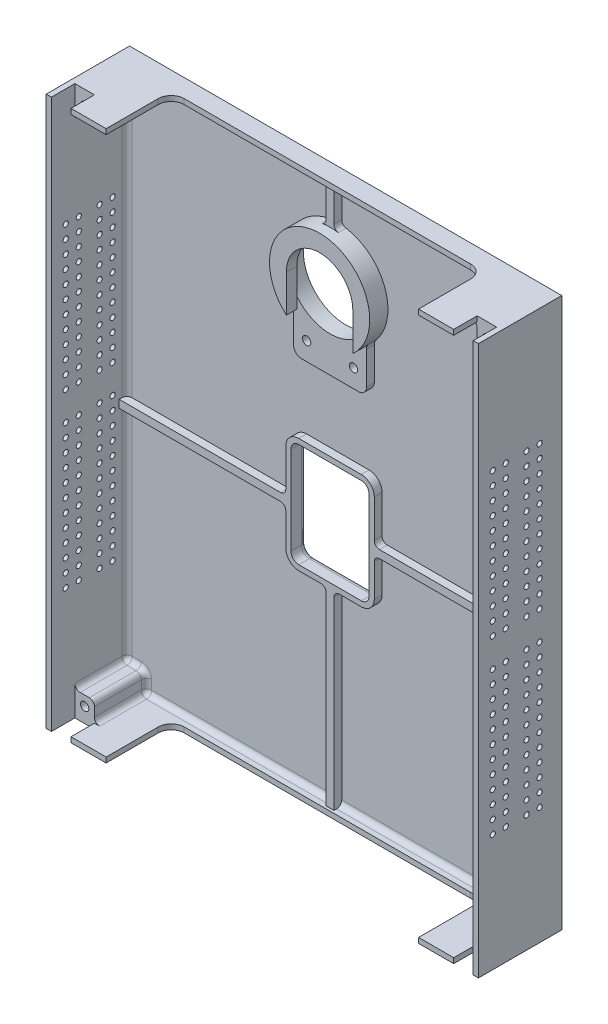
SolidWorks part; units mm, degrees
ref_plane "Front Plane" through (0, 0, 0) normal (0, 0, 1) x (1, 0, 0)
ref_plane "Top Plane" through (0, 0, 0) normal (0, 1, 0) x (1, 0, 0)
ref_plane "Right Plane" through (0, 0, 0) normal (1, 0, 0) x (0, 0, -1)
ref_plane "Plane1" through (0, 0, -1) normal (0, 0, 1) x (1, 0, 0)
sketch "Sketch5" plane through (0, 0, -1) normal (0, 0, 1) x (1, 0, 0)
  line L0 (100, 83.2573) -> (100, -169.2647) construction
  line L2 (17, 83.2573) -> (17, -127.7573)
  line L3 (17, -127.7573) -> (183, -127.7573)
  line L4 (183, 83.2573) -> (183, -127.7573)
  line L5 (17, 83.2573) -> (183, 83.2573)
  circle A0 centre (100, 48.2573) radius 16.25
  point P17 (45, 83.2573)
  dimension "D1" = 166
  dimension "D2" = 83
extrude "Boss-Extrude5" add sketch "Sketch5" along normal blind 3
sketch "Sketch6" plane through (0, 0, 2) normal (0, 0, 1) x (1, 0, 0)
  line L0 (116.25, 48.2573) -> (83.75, 48.2573) construction
  line L2 (86, 35.0451) -> (86, 18.2573)
  line L3 (86, 18.2573) -> (114, 18.2573)
  line L4 (114, 35.0451) -> (114, 18.2573)
  line L5 (100, 48.2573) -> (100, 52.872) construction
  circle A1 centre (100, 48.2573) radius 16.25
  arc A2 (114, 35.0451) -> (86, 35.0451) centre (100, 48.2573) ccw
  circle A6 centre (100, 48.2573) radius 16.25 construction
extrude "Boss-Extrude6" add sketch "Sketch6" along normal blind 3
sketch "Sketch7" plane through (0, 0, 5) normal (0, 0, 1) x (1, 0, 0)
  line L0 (112.75, 33.8351) -> (112.75, 48.2573)
  line L2 (87.25, 48.2573) -> (87.25, 33.8351)
  line L3 (100, 64.5073) -> (100, 48.2573) construction
  line L4 (100, 48.2573) -> (116.25, 48.2573) construction
  arc A8 (112.75, 33.8351) -> (87.25, 33.8351) centre (100, 48.2573) ccw
  circle A9 centre (100, 48.2573) radius 19.25 construction
  circle A10 centre (100, 48.2573) radius 16.25 construction
  circle A12 centre (100, 48.2573) radius 12.75
  arc A13 (112.75, 48.2573) -> (87.25, 48.2573) centre (100, 48.2573) ccw
  dimension "D1" = 1
extrude "Boss-Extrude7" add sketch "Sketch7" along normal blind 4
sketch "Sketch8" plane through (0, 0, 2) normal (0, 0, 1) x (1, 0, 0)
  line L4 (17, -127.7573) -> (183, -127.7573)
  line L5 (183, -127.7573) -> (183, 83.2573)
  line L6 (183, 83.2573) -> (17, 83.2573)
  line L7 (17, 83.2573) -> (17, -127.7573)
  line L8 (17, -127.7573) -> (183, -127.7573)
  line L9 (183, -127.7573) -> (183, 83.2573)
  line L10 (183, 83.2573) -> (17, 83.2573)
  line L11 (17, 83.2573) -> (17, -127.7573)
  line L12 (19, -125.7573) -> (181, -125.7573)
  line L13 (181, -125.7573) -> (181, 81.2573)
  line L14 (181, 81.2573) -> (19, 81.2573)
  line L15 (19, 81.2573) -> (19, -125.7573)
  dimension "D1" = 0
  dimension "D2" = 2
extrude "Boss-Extrude8" add sketch "Sketch8" along normal blind 29
fillet "Fillet2" radius 3 4 edges at (114, 18.2573, 3.5) (114, 35.0451, 3.5) (86, 18.2573, 3.5) (86, 35.0451, 3.5)
sketch "Sketch9" plane through (0, 0, 5) normal (0, 0, 1) x (1, 0, 0)
  line L0 (100, 48.2573) -> (100, 25.2573) construction
  line L1 (91, 25.2573) -> (109, 25.2573) construction
  line L2 (100, 25.2573) -> (100, 23.2329) construction
  circle A0 centre (91, 25.2573) radius 1.6
  circle A1 centre (109, 25.2573) radius 1.6
extrude "Cut-Extrude1" cut sketch "Sketch9" against normal up to surface (6 mm away) up to face at (100, -22.25, -1)
sketch "Sketch12" plane through (183, 0, 0) normal (1, 0, 0) x (0, 0, -1)
  circle A0 centre (-12.5, -16.7427) radius 1
  circle A1 centre (-7.5, -16.7427) radius 1
  circle A2 centre (-7.5, -11.7427) radius 1
  circle A3 centre (-7.5, -6.7427) radius 1
  circle A4 centre (-7.5, -1.7427) radius 1
  circle A5 centre (-7.5, 3.2573) radius 1
  circle A6 centre (-7.5, 8.2573) radius 1
  circle A7 centre (-7.5, 13.2573) radius 1
  circle A8 centre (-7.5, 18.2573) radius 1
  circle A9 centre (-7.5, 23.2573) radius 1
  circle A10 centre (-7.5, 28.2573) radius 1
  circle A11 centre (-7.5, 33.2573) radius 1
  circle A12 centre (-7.5, 38.2573) radius 1
  circle A13 centre (-12.5, -11.7427) radius 1
  circle A14 centre (-12.5, -6.7427) radius 1
  circle A15 centre (-12.5, -1.7427) radius 1
  circle A16 centre (-12.5, 3.2573) radius 1
  circle A17 centre (-12.5, 8.2573) radius 1
  circle A18 centre (-12.5, 13.2573) radius 1
  circle A19 centre (-12.5, 18.2573) radius 1
  circle A20 centre (-12.5, 23.2573) radius 1
  circle A21 centre (-12.5, 28.2573) radius 1
  circle A22 centre (-12.5, 33.2573) radius 1
  circle A23 centre (-12.5, 38.2573) radius 1
  circle A24 centre (-12.5, -82.7573) radius 1
  circle A25 centre (-12.5, -77.7573) radius 1
  circle A26 centre (-12.5, -72.7573) radius 1
  circle A27 centre (-12.5, -67.7573) radius 1
  circle A28 centre (-12.5, -62.7573) radius 1
  circle A29 centre (-12.5, -57.7573) radius 1
  circle A30 centre (-12.5, -52.7573) radius 1
  circle A31 centre (-12.5, -47.7573) radius 1
  circle A32 centre (-12.5, -42.7573) radius 1
  circle A33 centre (-12.5, -37.7573) radius 1
  circle A34 centre (-12.5, -32.7573) radius 1
  circle A35 centre (-7.5, -82.7573) radius 1
  circle A36 centre (-7.5, -77.7573) radius 1
  circle A37 centre (-7.5, -72.7573) radius 1
  circle A38 centre (-7.5, -67.7573) radius 1
  circle A39 centre (-7.5, -62.7573) radius 1
  circle A40 centre (-7.5, -57.7573) radius 1
  circle A41 centre (-7.5, -52.7573) radius 1
  circle A42 centre (-7.5, -47.7573) radius 1
  circle A43 centre (-7.5, -42.7573) radius 1
  circle A44 centre (-7.5, -37.7573) radius 1
  circle A45 centre (-7.5, -32.7573) radius 1
  circle A46 centre (-7.5, -27.7573) radius 1
  circle A47 centre (-12.5, -27.7573) radius 1
  circle A48 centre (-20.5, -27.7573) radius 1
  circle A49 centre (-25.5, -27.7573) radius 1
  circle A50 centre (-25.5, -32.7573) radius 1
  circle A51 centre (-25.5, -37.7573) radius 1
  circle A52 centre (-25.5, -42.7573) radius 1
  circle A53 centre (-25.5, -47.7573) radius 1
  circle A54 centre (-25.5, -52.7573) radius 1
  circle A55 centre (-25.5, -57.7573) radius 1
  circle A56 centre (-25.5, -62.7573) radius 1
  circle A57 centre (-25.5, -67.7573) radius 1
  circle A58 centre (-25.5, -72.7573) radius 1
  circle A59 centre (-25.5, -77.7573) radius 1
  circle A60 centre (-25.5, -82.7573) radius 1
  circle A61 centre (-20.5, -32.7573) radius 1
  circle A62 centre (-20.5, -37.7573) radius 1
  circle A63 centre (-20.5, -42.7573) radius 1
  circle A64 centre (-20.5, -47.7573) radius 1
  circle A65 centre (-20.5, -52.7573) radius 1
  circle A66 centre (-20.5, -57.7573) radius 1
  circle A67 centre (-20.5, -62.7573) radius 1
  circle A68 centre (-20.5, -67.7573) radius 1
  circle A69 centre (-20.5, -72.7573) radius 1
  circle A70 centre (-20.5, -77.7573) radius 1
  circle A71 centre (-20.5, -82.7573) radius 1
  circle A72 centre (-20.5, 38.2573) radius 1
  circle A73 centre (-20.5, 33.2573) radius 1
  circle A74 centre (-20.5, 28.2573) radius 1
  circle A75 centre (-20.5, 23.2573) radius 1
  circle A76 centre (-20.5, 18.2573) radius 1
  circle A77 centre (-20.5, 13.2573) radius 1
  circle A78 centre (-20.5, 8.2573) radius 1
  circle A79 centre (-20.5, 3.2573) radius 1
  circle A80 centre (-20.5, -1.7427) radius 1
  circle A81 centre (-20.5, -6.7427) radius 1
  circle A82 centre (-20.5, -11.7427) radius 1
  circle A83 centre (-25.5, 38.2573) radius 1
  circle A84 centre (-25.5, 33.2573) radius 1
  circle A85 centre (-25.5, 28.2573) radius 1
  circle A86 centre (-25.5, 23.2573) radius 1
  circle A87 centre (-25.5, 18.2573) radius 1
  circle A88 centre (-25.5, 13.2573) radius 1
  circle A89 centre (-25.5, 8.2573) radius 1
  circle A90 centre (-25.5, 3.2573) radius 1
  circle A91 centre (-25.5, -1.7427) radius 1
  circle A92 centre (-25.5, -6.7427) radius 1
  circle A93 centre (-25.5, -11.7427) radius 1
  circle A94 centre (-25.5, -16.7427) radius 1
  circle A95 centre (-20.5, -16.7427) radius 1
  dimension "D1" = 2
  dimension "D2" = 12
extrude "Cut-Extrude4" cut sketch "Sketch12" against normal up to surface (2 mm away) up to face at (181, -22.25, 16.5)
sketch "Sketch13" plane through (0, 0, -1) normal (0, 0, -1) x (-1, 0, 0)
  line L0 (-183, -30.7808) -> (-100, -30.7808) construction
  line L1 (-183, -127.7573) -> (-183, 83.2573) construction
  line L6 (-100, 83.2573) -> (-100, -30.7808) construction
  line L7 (-183, 83.2573) -> (-17, 83.2573) construction
  line L14 (-85, -47.7808) -> (-85, -13.7808)
  line L15 (-88, -10.7808) -> (-112, -10.7808)
  line L16 (-115, -13.7808) -> (-115, -47.7808)
  line L17 (-112, -50.7808) -> (-88, -50.7808)
  circle A1 centre (-100, -30.7808) radius 9 construction
  arc A15 (-88, -50.7808) -> (-85, -47.7808) centre (-88, -47.7808) ccw
  arc A16 (-85, -13.7808) -> (-88, -10.7808) centre (-88, -13.7808) ccw
  arc A17 (-112, -10.7808) -> (-115, -13.7808) centre (-112, -13.7808) ccw
  arc A18 (-115, -47.7808) -> (-112, -50.7808) centre (-112, -47.7808) ccw
extrude "Cut-Extrude5" cut sketch "Sketch13" against normal blind 3
sketch "Sketch14" plane through (17, 0, 0) normal (-1, 0, 0) x (0, 0, 1)
  circle A1 centre (12.5, -82.7573) radius 1
  circle A2 centre (12.5, -82.7573) radius 1
  circle A3 centre (12.5, -16.7427) radius 1
  circle A4 centre (12.5, -16.7427) radius 1
  circle A5 centre (7.5, 18.2573) radius 1
  circle A6 centre (7.5, 18.2573) radius 1
  circle A7 centre (7.5, 13.2573) radius 1
  circle A8 centre (7.5, 13.2573) radius 1
  circle A9 centre (7.5, 8.2573) radius 1
  circle A10 centre (7.5, 8.2573) radius 1
  circle A11 centre (7.5, 3.2573) radius 1
  circle A12 centre (7.5, 3.2573) radius 1
  circle A13 centre (7.5, -1.7427) radius 1
  circle A14 centre (7.5, -1.7427) radius 1
  circle A15 centre (7.5, -6.7427) radius 1
  circle A16 centre (7.5, -6.7427) radius 1
  circle A17 centre (7.5, -11.7427) radius 1
  circle A18 centre (7.5, -11.7427) radius 1
  circle A19 centre (7.5, -16.7427) radius 1
  circle A20 centre (7.5, -16.7427) radius 1
  circle A21 centre (12.5, 3.2573) radius 1
  circle A22 centre (12.5, 3.2573) radius 1
  circle A23 centre (12.5, -1.7427) radius 1
  circle A24 centre (12.5, -1.7427) radius 1
  circle A25 centre (12.5, -6.7427) radius 1
  circle A26 centre (12.5, -6.7427) radius 1
  circle A27 centre (12.5, -11.7427) radius 1
  circle A28 centre (12.5, -11.7427) radius 1
  circle A29 centre (7.5, 38.2573) radius 1
  circle A30 centre (7.5, 38.2573) radius 1
  circle A31 centre (7.5, 33.2573) radius 1
  circle A32 centre (7.5, 33.2573) radius 1
  circle A33 centre (7.5, 28.2573) radius 1
  circle A34 centre (7.5, 28.2573) radius 1
  circle A35 centre (7.5, 23.2573) radius 1
  circle A36 centre (7.5, 23.2573) radius 1
  circle A37 centre (12.5, -77.7573) radius 1
  circle A38 centre (12.5, -77.7573) radius 1
  circle A39 centre (12.5, 38.2573) radius 1
  circle A40 centre (12.5, 38.2573) radius 1
  circle A41 centre (12.5, 33.2573) radius 1
  circle A42 centre (12.5, 33.2573) radius 1
  circle A43 centre (12.5, 28.2573) radius 1
  circle A44 centre (12.5, 28.2573) radius 1
  circle A45 centre (12.5, 23.2573) radius 1
  circle A46 centre (12.5, 23.2573) radius 1
  circle A47 centre (12.5, 18.2573) radius 1
  circle A48 centre (12.5, 18.2573) radius 1
  circle A49 centre (12.5, 13.2573) radius 1
  circle A50 centre (12.5, 13.2573) radius 1
  circle A51 centre (12.5, 8.2573) radius 1
  circle A52 centre (12.5, 8.2573) radius 1
  circle A53 centre (12.5, -37.7573) radius 1
  circle A54 centre (12.5, -37.7573) radius 1
  circle A55 centre (12.5, -42.7573) radius 1
  circle A56 centre (12.5, -42.7573) radius 1
  circle A57 centre (12.5, -47.7573) radius 1
  circle A58 centre (12.5, -47.7573) radius 1
  circle A59 centre (12.5, -52.7573) radius 1
  circle A60 centre (12.5, -52.7573) radius 1
  circle A61 centre (12.5, -57.7573) radius 1
  circle A62 centre (12.5, -57.7573) radius 1
  circle A63 centre (12.5, -62.7573) radius 1
  circle A64 centre (12.5, -62.7573) radius 1
  circle A65 centre (12.5, -67.7573) radius 1
  circle A66 centre (12.5, -67.7573) radius 1
  circle A67 centre (12.5, -72.7573) radius 1
  circle A68 centre (12.5, -72.7573) radius 1
  circle A69 centre (7.5, -52.7573) radius 1
  circle A70 centre (7.5, -52.7573) radius 1
  circle A71 centre (7.5, -57.7573) radius 1
  circle A72 centre (7.5, -57.7573) radius 1
  circle A73 centre (7.5, -62.7573) radius 1
  circle A74 centre (7.5, -62.7573) radius 1
  circle A75 centre (7.5, -67.7573) radius 1
  circle A76 centre (7.5, -67.7573) radius 1
  circle A77 centre (7.5, -72.7573) radius 1
  circle A78 centre (7.5, -72.7573) radius 1
  circle A79 centre (7.5, -77.7573) radius 1
  circle A80 centre (7.5, -77.7573) radius 1
  circle A81 centre (7.5, -82.7573) radius 1
  circle A82 centre (7.5, -82.7573) radius 1
  circle A83 centre (12.5, -32.7573) radius 1
  circle A84 centre (12.5, -32.7573) radius 1
  circle A85 centre (25.5, -27.7573) radius 1
  circle A86 centre (25.5, -27.7573) radius 1
  circle A87 centre (20.5, -27.7573) radius 1
  circle A88 centre (20.5, -27.7573) radius 1
  circle A89 centre (12.5, -27.7573) radius 1
  circle A90 centre (12.5, -27.7573) radius 1
  circle A91 centre (7.5, -27.7573) radius 1
  circle A92 centre (7.5, -27.7573) radius 1
  circle A93 centre (7.5, -32.7573) radius 1
  circle A94 centre (7.5, -32.7573) radius 1
  circle A95 centre (7.5, -37.7573) radius 1
  circle A96 centre (7.5, -37.7573) radius 1
  circle A97 centre (7.5, -42.7573) radius 1
  circle A98 centre (7.5, -42.7573) radius 1
  circle A99 centre (7.5, -47.7573) radius 1
  circle A100 centre (7.5, -47.7573) radius 1
  circle A101 centre (25.5, -67.7573) radius 1
  circle A102 centre (25.5, -67.7573) radius 1
  circle A103 centre (25.5, -62.7573) radius 1
  circle A104 centre (25.5, -62.7573) radius 1
  circle A105 centre (25.5, -57.7573) radius 1
  circle A106 centre (25.5, -57.7573) radius 1
  circle A107 centre (25.5, -52.7573) radius 1
  circle A108 centre (25.5, -52.7573) radius 1
  circle A109 centre (25.5, -47.7573) radius 1
  circle A110 centre (25.5, -47.7573) radius 1
  circle A111 centre (25.5, -42.7573) radius 1
  circle A112 centre (25.5, -42.7573) radius 1
  circle A113 centre (25.5, -37.7573) radius 1
  circle A114 centre (25.5, -37.7573) radius 1
  circle A115 centre (25.5, -32.7573) radius 1
  circle A116 centre (25.5, -32.7573) radius 1
  circle A117 centre (20.5, -52.7573) radius 1
  circle A118 centre (20.5, -52.7573) radius 1
  circle A119 centre (20.5, -47.7573) radius 1
  circle A120 centre (20.5, -47.7573) radius 1
  circle A121 centre (20.5, -42.7573) radius 1
  circle A122 centre (20.5, -42.7573) radius 1
  circle A123 centre (20.5, -37.7573) radius 1
  circle A124 centre (20.5, -37.7573) radius 1
  circle A125 centre (20.5, -32.7573) radius 1
  circle A126 centre (20.5, -32.7573) radius 1
  circle A127 centre (25.5, -82.7573) radius 1
  circle A128 centre (25.5, -82.7573) radius 1
  circle A129 centre (25.5, -77.7573) radius 1
  circle A130 centre (25.5, -77.7573) radius 1
  circle A131 centre (25.5, -72.7573) radius 1
  circle A132 centre (25.5, -72.7573) radius 1
  circle A133 centre (20.5, 33.2573) radius 1
  circle A134 centre (20.5, 33.2573) radius 1
  circle A135 centre (20.5, 38.2573) radius 1
  circle A136 centre (20.5, 38.2573) radius 1
  circle A137 centre (20.5, -82.7573) radius 1
  circle A138 centre (20.5, -82.7573) radius 1
  circle A139 centre (20.5, -77.7573) radius 1
  circle A140 centre (20.5, -77.7573) radius 1
  circle A141 centre (20.5, -72.7573) radius 1
  circle A142 centre (20.5, -72.7573) radius 1
  circle A143 centre (20.5, -67.7573) radius 1
  circle A144 centre (20.5, -67.7573) radius 1
  circle A145 centre (20.5, -62.7573) radius 1
  circle A146 centre (20.5, -62.7573) radius 1
  circle A147 centre (20.5, -57.7573) radius 1
  circle A148 centre (20.5, -57.7573) radius 1
  circle A149 centre (20.5, -6.7427) radius 1
  circle A150 centre (20.5, -6.7427) radius 1
  circle A151 centre (20.5, -1.7427) radius 1
  circle A152 centre (20.5, -1.7427) radius 1
  circle A153 centre (20.5, 3.2573) radius 1
  circle A154 centre (20.5, 3.2573) radius 1
  circle A155 centre (20.5, 8.2573) radius 1
  circle A156 centre (20.5, 8.2573) radius 1
  circle A157 centre (20.5, 13.2573) radius 1
  circle A158 centre (20.5, 13.2573) radius 1
  circle A159 centre (20.5, 18.2573) radius 1
  circle A160 centre (20.5, 18.2573) radius 1
  circle A161 centre (20.5, 23.2573) radius 1
  circle A162 centre (20.5, 23.2573) radius 1
  circle A163 centre (20.5, 28.2573) radius 1
  circle A164 centre (20.5, 28.2573) radius 1
  circle A165 centre (25.5, 8.2573) radius 1
  circle A166 centre (25.5, 8.2573) radius 1
  circle A167 centre (25.5, 13.2573) radius 1
  circle A168 centre (25.5, 13.2573) radius 1
  circle A169 centre (25.5, 18.2573) radius 1
  circle A170 centre (25.5, 18.2573) radius 1
  circle A171 centre (25.5, 23.2573) radius 1
  circle A172 centre (25.5, 23.2573) radius 1
  circle A173 centre (25.5, 28.2573) radius 1
  circle A174 centre (25.5, 28.2573) radius 1
  circle A175 centre (25.5, 33.2573) radius 1
  circle A176 centre (25.5, 33.2573) radius 1
  circle A177 centre (25.5, 38.2573) radius 1
  circle A178 centre (25.5, 38.2573) radius 1
  circle A179 centre (20.5, -11.7427) radius 1
  circle A180 centre (20.5, -11.7427) radius 1
  circle A181 centre (20.5, -16.7427) radius 1
  circle A182 centre (20.5, -16.7427) radius 1
  circle A183 centre (25.5, -16.7427) radius 1
  circle A184 centre (25.5, -16.7427) radius 1
  circle A185 centre (25.5, -11.7427) radius 1
  circle A186 centre (25.5, -11.7427) radius 1
  circle A187 centre (25.5, -6.7427) radius 1
  circle A188 centre (25.5, -6.7427) radius 1
  circle A189 centre (25.5, -1.7427) radius 1
  circle A190 centre (25.5, -1.7427) radius 1
  circle A191 centre (25.5, 3.2573) radius 1
  circle A192 centre (25.5, 3.2573) radius 1
  dimension "D1" = 0
  dimension "D2" = 0
  dimension "D3" = 0
  dimension "D4" = 0
  dimension "D5" = 0
  dimension "D6" = 0
  dimension "D7" = 0
  dimension "D8" = 0
  dimension "D9" = 0
  dimension "D10" = 0
  dimension "D11" = 0
  dimension "D12" = 0
  dimension "D13" = 0
  dimension "D14" = 0
  dimension "D15" = 0
  dimension "D16" = 0
  dimension "D17" = 0
  dimension "D18" = 0
  dimension "D19" = 0
  dimension "D20" = 0
  dimension "D21" = 0
  dimension "D22" = 0
  dimension "D23" = 0
  dimension "D24" = 0
  dimension "D25" = 0
  dimension "D26" = 0
  dimension "D27" = 0
  dimension "D28" = 0
  dimension "D29" = 0
  dimension "D30" = 0
  dimension "D31" = 0
  dimension "D32" = 0
  dimension "D33" = 0
  dimension "D34" = 0
  dimension "D35" = 0
  dimension "D36" = 0
  dimension "D37" = 0
  dimension "D38" = 0
  dimension "D39" = 0
  dimension "D40" = 0
  dimension "D41" = 0
  dimension "D42" = 0
  dimension "D43" = 0
  dimension "D44" = 0
  dimension "D45" = 0
  dimension "D46" = 0
  dimension "D47" = 0
  dimension "D48" = 0
  dimension "D49" = 0
  dimension "D50" = 0
  dimension "D51" = 0
  dimension "D52" = 0
  dimension "D53" = 0
  dimension "D54" = 0
  dimension "D55" = 0
  dimension "D56" = 0
  dimension "D57" = 0
  dimension "D58" = 0
  dimension "D59" = 0
  dimension "D60" = 0
  dimension "D61" = 0
  dimension "D62" = 0
  dimension "D63" = 0
  dimension "D64" = 0
  dimension "D65" = 0
  dimension "D66" = 0
  dimension "D67" = 0
  dimension "D68" = 0
  dimension "D69" = 0
  dimension "D70" = 0
  dimension "D71" = 0
  dimension "D72" = 0
  dimension "D73" = 0
  dimension "D74" = 0
  dimension "D75" = 0
  dimension "D76" = 0
  dimension "D77" = 0
  dimension "D78" = 0
  dimension "D79" = 0
  dimension "D80" = 0
  dimension "D81" = 0
  dimension "D82" = 0
  dimension "D83" = 0
  dimension "D84" = 0
  dimension "D85" = 0
  dimension "D86" = 0
  dimension "D87" = 0
  dimension "D88" = 0
  dimension "D89" = 0
  dimension "D90" = 0
  dimension "D91" = 0
  dimension "D92" = 0
  dimension "D93" = 0
  dimension "D94" = 0
  dimension "D95" = 0
  dimension "D96" = 0
extrude "Cut-Extrude6" cut sketch "Sketch14" against normal up to surface (2 mm away) up to face at (19, -22.25, 16.5)
sketch "Sketch15" plane through (0, -127.7573, 0) normal (0, -1, 0) x (1, 0, 0)
  line L5 (100, -1) -> (100, 31) construction
  line L6 (17, -1) -> (183, -1) construction
  line L7 (17, 31) -> (183, 31) construction
  line L8 (40, 31) -> (160, 31)
  line L9 (40, 31) -> (40, 11)
  line L10 (45, 6) -> (155, 6)
  line L11 (160, 31) -> (160, 11)
  arc A4 (155, 6) -> (160, 11) centre (155, 11) ccw
  arc A5 (40, 11) -> (45, 6) centre (45, 11) ccw
  point P12 (160, 6)
  point P15 (40, 6)
  dimension "D4" = 5
  dimension "D1" = 60
  dimension "D2" = 120
  dimension "D3" = 25
extrude "Cut-Extrude7" cut sketch "Sketch15" against normal up to surface (2 mm away) up to face at (100, -125.7573, 16.5)
sketch "Sketch16" plane through (0, 83.2573, 0) normal (0, 1, 0) x (1, 0, 0)
  line L4 (40, -31) -> (160, -31)
  line L5 (40, -31) -> (160, -31)
  line L6 (160, -31) -> (160, -11)
  line L7 (160, -31) -> (160, -11)
  line L12 (155, -6) -> (45, -6)
  line L13 (155, -6) -> (45, -6)
  line L14 (40, -11) -> (40, -31)
  line L15 (40, -11) -> (40, -31)
  arc A2 (160, -11) -> (155, -6) centre (155, -11) ccw
  arc A3 (160, -11) -> (155, -6) centre (155, -11) ccw
  arc A4 (45, -6) -> (40, -11) centre (45, -11) ccw
  arc A5 (45, -6) -> (40, -11) centre (45, -11) ccw
  dimension "D1" = 0
extrude "Cut-Extrude8" cut sketch "Sketch16" against normal up to surface (2 mm away) up to face at (100, 81.2573, 16.5)
sketch "Sketch18" plane through (0, 0, 2) normal (0, 0, 1) x (1, 0, 0)
  line L1 (19, -125.7573) -> (26.5, -125.7573)
  line L2 (19, -125.7573) -> (19, -118.2573)
  line L3 (19, -118.2573) -> (26.5, -118.2573)
  line L4 (26.5, -125.7573) -> (26.5, -118.2573)
  line L5 (181, -125.7573) -> (173.5, -125.7573)
  line L6 (181, -125.7573) -> (181, -118.2573)
  line L7 (181, -118.2573) -> (173.5, -118.2573)
  line L8 (173.5, -125.7573) -> (173.5, -118.2573)
  line L9 (19, 81.2573) -> (26.5, 81.2573)
  line L10 (19, 81.2573) -> (19, 73.7573)
  line L11 (19, 73.7573) -> (26.5, 73.7573)
  line L12 (26.5, 81.2573) -> (26.5, 73.7573)
  line L13 (181, 81.2573) -> (173.5, 81.2573)
  line L14 (181, 81.2573) -> (181, 73.7573)
  line L15 (181, 73.7573) -> (173.5, 73.7573)
  line L16 (173.5, 81.2573) -> (173.5, 73.7573)
extrude "Boss-Extrude10" add sketch "Sketch18" along normal blind 20
fillet "Fillet3" radius 2 12 edges at (181, 73.7573, 12) (173.5, 73.7573, 12) (173.5, 81.2573, 12) (26.5, 81.2573, 12) (26.5, 73.7573, 12) (19, 73.7573, 12) (19, -118.2573, 12) (26.5, -118.2573, 12) (26.5, -125.7573, 12) (181, -118.2573, 12) (173.5, -118.2573, 12) (173.5, -125.7573, 12)
sketch "Sketch19" plane through (0, 0, 22) normal (0, 0, 1) x (1, 0, 0)
  line L4 (100, -127.7573) -> (100, 83.2573) construction
  line L5 (45, -127.7573) -> (155, -127.7573) construction
  line L6 (155, 83.2573) -> (45, 83.2573) construction
  line L7 (100, -22.25) -> (17, -22.25) construction
  line L8 (17, 83.2573) -> (17, -127.7573) construction
  circle A0 centre (22.75, -122.0073) radius 1.6
  circle A1 centre (177.25, -122.0073) radius 1.6
  circle A2 centre (177.25, 77.5073) radius 1.6
  circle A3 centre (22.75, 77.5073) radius 1.6
extrude "Cut-Extrude9" cut sketch "Sketch19" against normal up to surface (23 mm away) up to face at (100, -30.7808, -1)
fillet "Fillet4" radius 2 24 edges at (180.4142, -117.6715, 2) (177.25, -118.2573, 2) (174.0858, -118.8431, 2) (173.5, -122.0073, 2) (172.9142, -125.1715, 2) (100, -125.7573, 2) (27.0858, -125.1715, 2) (26.5, -122.0073, 2) (25.9142, -118.8431, 2) (22.75, -118.2573, 2) (19.5858, -117.6715, 2) (19, -22.25, 2) (19.5858, 73.1715, 2) (22.75, 73.7573, 2) (25.9142, 74.3431, 2) (26.5, 77.5073, 2) (27.0858, 80.6715, 2) (100, 81.2573, 2) (172.9142, 80.6715, 2) (173.5, 77.5073, 2) (174.0858, 74.3431, 2) (177.25, 73.7573, 2) (180.4142, 73.1715, 2) (181, -22.25, 2)
sketch "Sketch20" plane through (0, 0, 2) normal (0, 0, 1) x (1, 0, 0)
  line L0 (83, -30.2573) -> (83, -13.7808)
  line L1 (155, 83.2573) -> (45, 83.2573) construction
  line L2 (45, -127.7573) -> (155, -127.7573) construction
  line L3 (88, -10.7808) -> (112, -10.7808) construction
  line L4 (101.5, -127.7573) -> (98.5, -127.7573)
  line L5 (101.5, -127.7573) -> (101.5, -52.7808)
  line L6 (101.5, 83.2573) -> (98.5, 83.2573)
  line L7 (98.5, -127.7573) -> (98.5, -52.7808)
  line L8 (115, -13.7808) -> (115, -47.7808) construction
  line L9 (112, -50.7808) -> (88, -50.7808) construction
  line L10 (85, -47.7808) -> (85, -13.7808) construction
  line L11 (88, -10.7808) -> (112, -10.7808)
  line L12 (115, -13.7808) -> (115, -47.7808)
  line L13 (112, -50.7808) -> (88, -50.7808)
  line L14 (85, -47.7808) -> (85, -13.7808)
  line L15 (88, -8.7808) -> (112, -8.7808)
  line L16 (117, -13.7808) -> (117, -30.2573)
  line L17 (112, -52.7808) -> (101.5, -52.7808)
  line L18 (83, -47.7808) -> (83, -33.2573)
  line L20 (183, -127.7573) -> (183, 83.2573) construction
  line L21 (183, -33.2573) -> (117, -33.2573)
  line L22 (183, -33.2573) -> (183, -30.2573)
  line L23 (183, -30.2573) -> (117, -30.2573)
  line L24 (17, -33.2573) -> (17, -30.2573)
  line L25 (17, 83.2573) -> (17, -127.7573) construction
  line L26 (83, -33.2573) -> (17, -33.2573)
  line L28 (98.5, -52.7808) -> (88, -52.7808)
  line L31 (83, -30.2573) -> (17, -30.2573)
  line L33 (112, -52.7808) -> (88, -52.7808) construction
  line L35 (117, -33.2573) -> (117, -47.7808)
  line L38 (117, -13.7808) -> (117, -47.7808) construction
  line L39 (88, -8.7808) -> (112, -8.7808) construction
  line L40 (83, -47.7808) -> (83, -13.7808) construction
  line L44 (98.5, 64.4379) -> (98.5, 83.2573)
  line L45 (101.5, 64.4379) -> (101.5, 83.2573)
  line L49 (112.75, 48.2573) -> (112.75, 38.1826)
  line L51 (87.25, 38.1826) -> (87.25, 48.2573)
  arc A0 (88, -10.7808) -> (85, -13.7808) centre (88, -13.7808) ccw construction
  arc A1 (115, -13.7808) -> (112, -10.7808) centre (112, -13.7808) ccw construction
  arc A2 (112, -50.7808) -> (115, -47.7808) centre (112, -47.7808) ccw construction
  arc A3 (85, -47.7808) -> (88, -50.7808) centre (88, -47.7808) ccw construction
  arc A4 (88, -10.7808) -> (85, -13.7808) centre (88, -13.7808) ccw
  arc A5 (115, -13.7808) -> (112, -10.7808) centre (112, -13.7808) ccw
  arc A6 (112, -50.7808) -> (115, -47.7808) centre (112, -47.7808) ccw
  arc A7 (85, -47.7808) -> (88, -50.7808) centre (88, -47.7808) ccw
  arc A8 (117, -13.7808) -> (112, -8.7808) centre (112, -13.7808) ccw
  arc A9 (112, -52.7808) -> (117, -47.7808) centre (112, -47.7808) ccw
  arc A10 (83, -47.7808) -> (88, -52.7808) centre (88, -47.7808) ccw
  arc A11 (88, -8.7808) -> (83, -13.7808) centre (88, -13.7808) ccw
  arc A14 (112.75, 48.2573) -> (87.25, 48.2573) centre (100, 48.2573) ccw
  arc A15 (112.75, 38.1826) -> (87.25, 38.1826) centre (100, 48.2573) ccw
  arc A18 (101.5, 64.4379) -> (98.5, 64.4379) centre (100, 48.2573) ccw
  dimension "D1" = 0
  dimension "D3" = 2
extrude "Boss-Extrude11" add sketch "Sketch20" along normal blind 3
fillet "Fillet5" radius 2 8 edges at (98.5, -52.7808, 3.5) (101.5, -52.7808, 3.5) (117, -33.2573, 3.5) (117, -30.2573, 3.5) (83, -33.2573, 3.5) (83, -30.2573, 3.5) (101.5, 67.4488, 3.5) (98.5, 67.4488, 3.5)
sketch "Sketch21" plane through (0, 0, -1) normal (0, 0, -1) x (-1, 0, 0)
  circle A0 centre (-109, 25.2573) radius 2.25
  circle A1 centre (-91, 25.2573) radius 2.25
extrude "Cut-Extrude10" cut sketch "Sketch21" against normal blind 3
fillet "Fillet6" radius 2 8 edges at (85.8787, -49.9021, -1) (100, -50.7808, -1) (114.1213, -49.9021, -1) (115, -30.7808, -1) (114.1213, -11.6594, -1) (100, -10.7808, -1) (85.8787, -11.6594, -1) (85, -30.7808, -1)
chamfer "Chamfer1" distance 1.5 angle 45 4 edges at (21.15, 77.5073, -1) (21.15, -122.0073, -1) (175.65, -122.0073, -1) (175.65, 77.5073, -1)
sketch "Sketch22" plane through (0, 0, 31) normal (0, 0, 1) x (1, 0, 0)
  line L0 (173.5, -120.2573) -> (173.5, -123.7573) construction
  line L1 (173.5, -125.7573) -> (173.5, -127.7573)
  line L3 (181, -125.7573) -> (173.5, -125.7573)
  line L4 (160, -127.7573) -> (183, -127.7573) construction
  line L5 (183, -127.7573) -> (183, 83.2573) construction
  line L7 (181, -127.7573) -> (173.5, -127.7573)
  line L8 (100, -127.7573) -> (100, 83.2573) construction
  line L9 (45, -127.7573) -> (155, -127.7573) construction
  line L10 (155, 83.2573) -> (45, 83.2573) construction
  line L11 (183, -22.25) -> (17, -22.25) construction
  line L12 (17, 83.2573) -> (17, -127.7573) construction
  line L13 (19, -127.7573) -> (26.5, -127.7573)
  line L15 (19, -125.7573) -> (26.5, -125.7573)
  line L16 (26.5, -125.7573) -> (26.5, -127.7573)
  line L17 (26.5, 81.2573) -> (26.5, 83.2573)
  line L18 (19, 81.2573) -> (26.5, 81.2573)
  line L20 (19, 83.2573) -> (26.5, 83.2573)
  line L21 (181, 83.2573) -> (173.5, 83.2573)
  line L23 (181, 81.2573) -> (173.5, 81.2573)
  line L24 (173.5, 81.2573) -> (173.5, 83.2573)
  line L25 (19, 83.2573) -> (19, 81.2573)
  line L26 (181, 83.2573) -> (181, 81.2573)
  line L27 (181, -125.7573) -> (181, -127.7573)
  line L28 (19, -125.7573) -> (19, -127.7573)
  dimension "D1" = 2
extrude "Cut-Extrude11" cut sketch "Sketch22" against normal up to surface (9 mm away) up to face at (21.15, 77.5073, 22)
